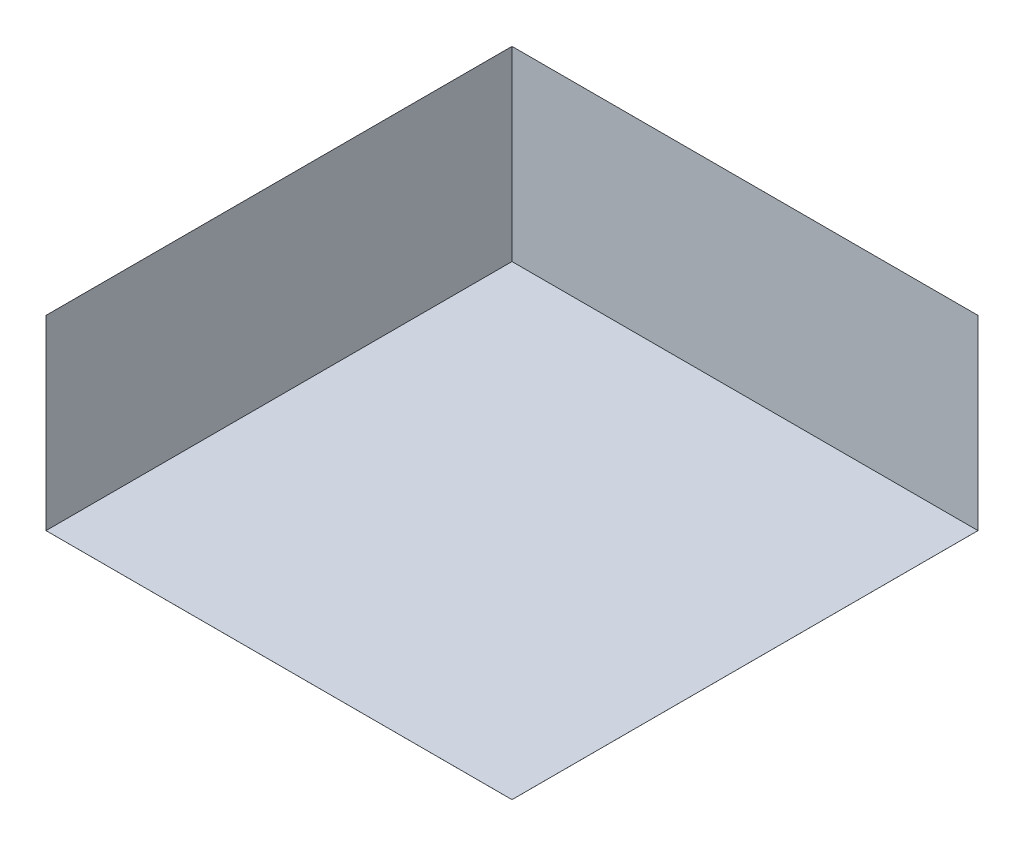
SolidWorks part; units mm, degrees
ref_plane "Front Plane" through (0, 0, 0) normal (0, 0, 1) x (1, 0, 0)
ref_plane "Top Plane" through (0, 0, 0) normal (0, 1, 0) x (1, 0, 0)
ref_plane "Right Plane" through (0, 0, 0) normal (1, 0, 0) x (0, 0, -1)
sketch "Sketch2" plane through (0, 0, 0) normal (0, 1, 0) x (1, 0, 0)
  line L1 (-53.3201, 19.4977) -> (4946.6799, 19.4977)
  line L2 (-53.3201, 19.4977) -> (-53.3201, -4980.5023)
  line L3 (-53.3201, -4980.5023) -> (4946.6799, -4980.5023)
  line L4 (4946.6799, 19.4977) -> (4946.6799, -4980.5023)
  dimension "Length_Floor" = 5000
  dimension "Width_Floor" = 5000
extrude "Floor" add sketch "Sketch2" along normal blind 0.254
sketch "Sketch3" plane through (0, 0.254, 0) normal (0, 1, 0) x (1, 0, 0)
  line L0 (4946.6799, 19.4977) -> (-53.3201, 19.4977) construction
  line L1 (4946.6799, 19.4977) -> (-53.3201, 19.4977)
  dimension "wallBase" = 5000
extrude "Wall1" add sketch "Sketch3" along normal blind 2000 separate body thin thin type one direction wall 0.0254
sketch "Sketch4" plane through (0, 0.254, 0) normal (0, 1, 0) x (1, 0, 0)
  line L0 (-53.3201, 19.4977) -> (-53.3201, -4980.5023) construction
  line L1 (-53.3201, 19.4977) -> (-53.3201, -4980.5023)
  dimension "wall2Base" = 5000
extrude "Wall2" add sketch "Sketch4" along normal blind 2000 separate body thin thin type one direction wall 0.0254
